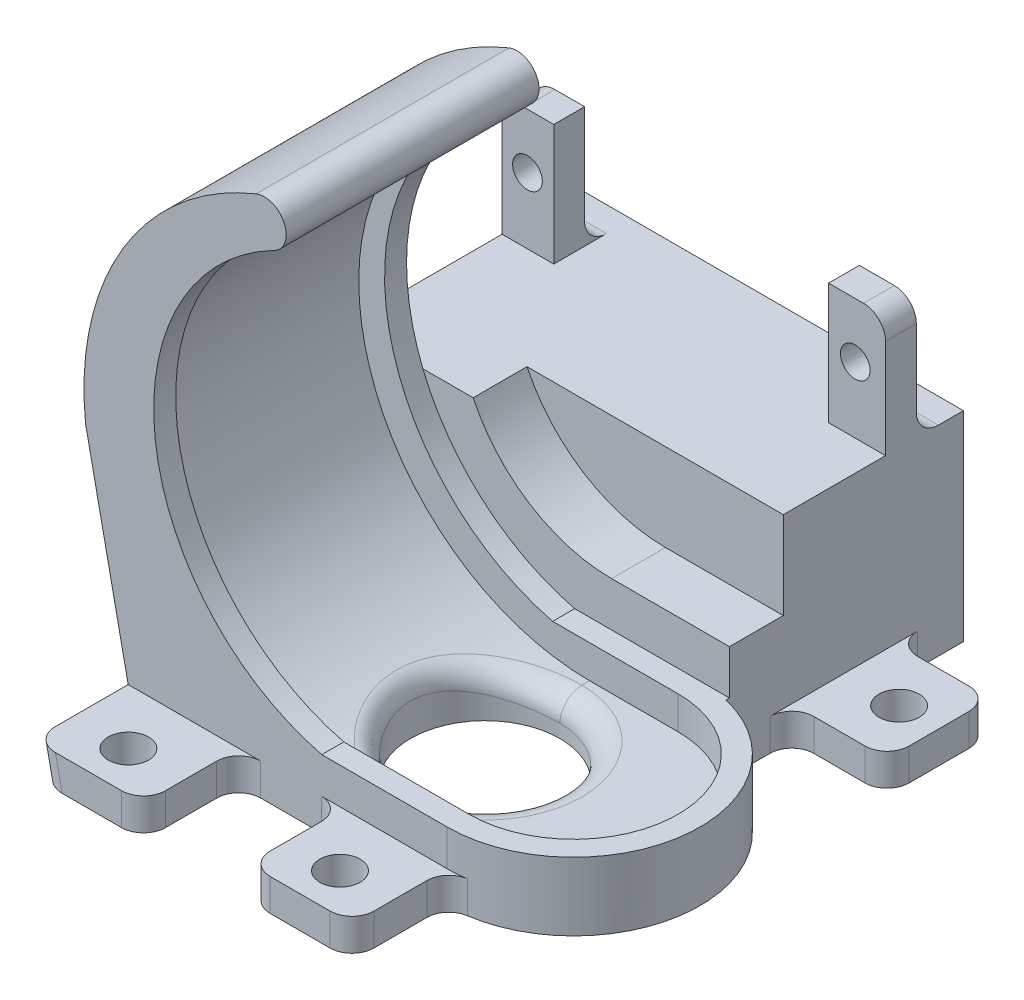
SolidWorks part; units mm, degrees
material "ABS"
ref_plane "Front Plane" through (0, 0, 0) normal (0, 0, 1) x (1, 0, 0)
ref_plane "Top Plane" through (0, 0, 0) normal (0, 1, 0) x (1, 0, 0)
ref_plane "Right Plane" through (0, 0, 0) normal (1, 0, 0) x (0, 0, -1)
sketch "Sketch1" plane through (0, 0, 0) normal (0, 1, 0) x (1, 0, 0)
  line L1 (-31.75, -12.065) -> (31.75, -12.065)
  line L2 (-31.75, -12.065) -> (-31.75, 12.065)
  line L3 (-31.75, 12.065) -> (31.75, 12.065)
  line L4 (31.75, -12.065) -> (31.75, 12.065)
  line L5 (-31.75, -12.065) -> (31.75, 12.065) construction
  line L6 (-31.75, 12.065) -> (31.75, -12.065) construction
  point P0 (0, 0)
  dimension "D1" = 24.13
  dimension "D2" = 63.5
extrude "Boss-Extrude1" add sketch "Sketch1" along normal blind 4.064
sketch "Sketch2" plane through (0, 0, 0) normal (0, 0, 1) x (1, 0, 0)
  line L0 (0, -2.2352) -> (0, 2.2352) construction
  line L1 (-31.75, 4.064) -> (31.75, 4.064) construction
  line L3 (-31.75, 4.064) -> (31.75, 4.064) construction
  line L4 (0, 4.064) -> (-26.7168, 4.064)
  line L5 (-31.571, 27.3677) -> (-26.7168, 4.064)
  arc A0 (-9.9723, 55.4695) -> (0, 4.064) centre (0, 30.734) ccw
  arc A1 (-11.8717, 60.181) -> (-31.571, 27.3677) centre (0, 30.734) ccw
  arc A2 (-9.9723, 55.4695) -> (-11.8717, 60.181) centre (-10.922, 57.8252) ccw
  dimension "D1" = 53.34
  dimension "D2" = 63.5
  dimension "D3" = 10.922
  dimension "D4" = 23.3037
  dimension "D5" = 23.8039
extrude "Boss-Extrude2" add sketch "Sketch2" along normal up to surface and the other way up to surface up to face at (0, 2.032, 12.065) other way up to face at (0, 2.032, -12.065)
sketch "Sketch4" plane through (0, 4.064, 0) normal (0, 1, 0) x (1, 0, 0)
  circle A0 centre (0, 0) radius 8.636
  dimension "D1" = 17.272
extrude "Cut-Extrude1" cut sketch "Sketch4" against normal through all and the other way blind 4.064
fillet "Fillet1" radius 2.54 2 edges at (8.636, 4.064, 0) (-8.5992, 5.4884, 0.7963)
sketch "Sketch6" plane through (0, 0, 12.065) normal (0, 0, 1) x (1, 0, 0)
  line L0 (-31.75, 4.064) -> (-26.7168, 4.064)
  line L1 (-26.7168, 4.064) -> (-25.8702, 0)
  line L2 (-25.8702, 0) -> (-31.75, 0)
  line L3 (-31.75, 4.064) -> (-31.75, 0) construction
  line L4 (-31.75, 0) -> (-31.75, 4.064)
  dimension "D1" = 4.1512
extrude "Cut-Extrude2" cut sketch "Sketch6" against normal through all
sketch "Sketch8" plane through (0, 0, 12.065) normal (0, 0, 1) x (1, 0, 0)
  line L0 (31.75, 0) -> (31.75, 7.874)
  line L1 (0, 4.064) -> (31.75, 4.064) construction
  line L2 (31.75, 0) -> (-25.8702, 0)
  line L3 (-25.8702, 0) -> (-31.571, 27.3677)
  line L4 (31.75, 7.874) -> (-23.9497, 7.874) construction
  line L5 (-4.2746, 7.874) -> (31.75, 7.874)
  arc A0 (-31.571, 27.3677) -> (-11.8717, 60.181) centre (0, 30.734) cw
  arc A1 (-11.8717, 60.181) -> (-9.9723, 55.4695) centre (-10.922, 57.8252) cw
  arc A2 (-9.9723, 55.4695) -> (-4.2746, 7.874) centre (1.9655, 32.7598) ccw
  dimension "D1" = 3.81
extrude "Boss-Extrude3" add sketch "Sketch8" along normal blind 2.54
sketch "Sketch9" plane through (0, 0, -12.065) normal (0, 0, -1) x (-1, 0, 0)
  line L0 (-31.75, 0) -> (-31.75, 7.874)
  line L1 (-31.75, 7.874) -> (4.2746, 7.874)
  line L2 (-31.75, 0) -> (25.8702, 0)
  line L3 (25.8702, 0) -> (31.571, 27.3677)
  arc A0 (31.571, 27.3677) -> (11.8717, 60.181) centre (0, 30.734) ccw
  arc A2 (9.9723, 55.4695) -> (4.2746, 7.874) centre (-1.9655, 32.7598) cw
  arc A3 (11.8717, 60.181) -> (9.9723, 55.4695) centre (10.922, 57.8252) ccw
extrude "Boss-Extrude4" add sketch "Sketch9" along normal blind 2.54
sketch "Sketch10" plane through (0, 4.064, 0) normal (0, 1, 0) x (1, 0, 0)
  line L0 (10.2183, 14.605) -> (10.2183, -14.605) construction
  line L3 (-4.2746, 14.605) -> (31.75, 14.605) construction
  line L4 (31.75, -14.605) -> (-4.2746, -14.605) construction
  line L5 (10.2183, 14.605) -> (10.2183, 12.065)
  line L6 (10.2183, -12.065) -> (10.2183, -14.605)
  arc A2 (10.2183, 14.605) -> (10.2183, -14.605) centre (10.2183, 0) cw
  arc A3 (10.2183, -12.065) -> (10.2183, 12.065) centre (10.2183, 0) ccw
extrude "Boss-Extrude5" add sketch "Sketch10" along normal blind 3.81
sketch "Sketch11" plane through (0, 7.874, 0) normal (0, 1, 0) x (1, 0, 0)
  line L0 (10.2183, 12.065) -> (10.2183, -12.065) construction
  line L1 (10.2183, 14.605) -> (10.2183, -14.605) construction
  line L2 (-4.2746, 14.605) -> (31.75, 14.605) construction
  line L3 (31.75, -14.605) -> (-4.2746, -14.605) construction
  line L4 (10.2183, 14.605) -> (31.75, 14.605)
  line L5 (31.75, 14.605) -> (31.75, -14.605)
  line L6 (31.75, -14.605) -> (10.2183, -14.605)
  arc A0 (10.2183, -14.605) -> (10.2183, 14.605) centre (10.2183, 0) ccw
extrude "Cut-Extrude3" cut sketch "Sketch11" against normal through all
sketch "Sketch12" plane through (0, 0, 0) normal (0, -1, 0) x (1, 0, 0)
  line L0 (-25.8702, -14.605) -> (-31.571, -14.605) construction
  line L1 (-31.2166, -14.605) -> (13.6144, -14.605)
  line L2 (-31.2166, -14.605) -> (-31.2166, -41.632)
  line L3 (-31.2166, -41.632) -> (13.6144, -41.632)
  line L4 (13.6144, -14.605) -> (13.6144, -41.632)
extrude "Boss-Extrude6" add sketch "Sketch12" against normal up to surface (23.114 mm away) up to face at (-6.2783, 14.6544, 12.065)
sketch "Sketch13" plane through (0, 0, 0) normal (0, -1, 0) x (1, 0, 0)
  line L0 (10.2183, -14.605) -> (13.6144, -14.605)
  line L1 (13.6144, -14.605) -> (13.6144, -13.3355)
  line L2 (13.6144, -13.3355) -> (10.2183, -14.605)
extrude "Boss-Extrude7" add sketch "Sketch13" against normal up to surface (7.874 mm away) up to face at (6.3056, 7.874, 0)
sketch "Sketch14" plane through (0, 0, -14.605) normal (0, 0, 1) x (1, 0, 0)
  line L0 (0, 13.0173) -> (18.6203, 13.0173)
  line L1 (18.6203, 13.0173) -> (17.7167, 30.734)
  arc A0 (17.7167, 30.734) -> (0, 13.0173) centre (0, 30.734) ccw
extrude "Cut-Extrude4" cut sketch "Sketch14" against normal up to surface (6.2198 mm away) up to face at (7.2796, 4.064, 0)
sketch "Sketch16" plane through (0, 0, -14.605) normal (0, 0, 1) x (1, 0, 0)
  line L0 (-31.2166, 23.114) -> (-30.685, 23.114)
  line L1 (-30.685, 23.114) -> (-25.8702, 0)
  line L2 (-25.8702, 0) -> (-31.2166, 0)
  line L3 (-31.2166, 0) -> (-31.2166, 23.114)
extrude "Cut-Extrude5" cut sketch "Sketch16" against normal up to surface (27.027 mm away) up to face at (-8.8011, 11.557, -41.632)
sketch "Sketch17" plane through (0, 23.114, 0) normal (0, 1, 0) x (1, 0, 0)
  line L0 (13.6144, 41.632) -> (13.6144, 20.8248) construction
  line L1 (6.6167, 32.6358) -> (13.6144, 32.6358)
  line L2 (6.6167, 32.6358) -> (6.6167, 36.1918)
  line L3 (6.6167, 36.1918) -> (13.6144, 36.1918)
  line L4 (13.6144, 32.6358) -> (13.6144, 36.1918)
  dimension "D1" = 3.556
extrude "Boss-Extrude8" add sketch "Sketch17" along normal blind 13.97
sketch "Sketch18" plane through (0, 23.114, 0) normal (0, 1, 0) x (1, 0, 0)
  line L0 (-30.685, 41.632) -> (-30.685, 14.605) construction
  line L1 (-24.2951, 32.6358) -> (-30.685, 32.6358)
  line L2 (-24.2951, 32.6358) -> (-24.2951, 36.1918)
  line L3 (-24.2951, 36.1918) -> (-30.685, 36.1918)
  line L4 (-30.685, 32.6358) -> (-30.685, 36.1918)
  dimension "D1" = 3.556
extrude "Boss-Extrude9" add sketch "Sketch18" along normal blind 13.97
sketch "Sketch19" plane through (0, 37.084, 0) normal (0, 1, 0) x (1, 0, 0)
  line L0 (-24.2951, 36.1918) -> (6.6167, 36.1918) construction
  line L1 (6.6167, 32.6358) -> (13.6144, 32.6358) construction
  line L2 (-24.7142, 39.7478) -> (7.0358, 39.7478)
  line L3 (-24.7142, 39.7478) -> (-24.7142, 32.6358)
  line L4 (-24.7142, 32.6358) -> (7.0358, 32.6358)
  line L5 (7.0358, 39.7478) -> (7.0358, 32.6358)
  line L6 (-24.7142, 39.7478) -> (7.0358, 32.6358) construction
  line L7 (-24.7142, 32.6358) -> (7.0358, 39.7478) construction
  point P4 (-8.8392, 36.1918)
  dimension "D1" = 31.75
extrude "Cut-Extrude6" cut sketch "Sketch19" against normal up to surface (13.97 mm away) up to face at (-10.4957, 23.114, -29.6026)
sketch "Sketch20" plane through (0, 0, -36.1918) normal (0, 0, -1) x (-1, 0, 0)
  circle A0 centre (27.7559, 30.734) radius 1.7145
  circle A1 centre (-10.1155, 30.734) radius 1.7145
  dimension "D1" = 3.429
  dimension "D2" = 3.429
extrude "Cut-Extrude7" cut sketch "Sketch20" against normal up to surface (3.556 mm away)
fillet "Fillet2" radius 2.54 1 edges at (10.3251, 23.114, -36.1918)
fillet "Fillet3" radius 2.54 1 edges at (-27.6996, 23.114, -36.1918)
fillet "Fillet4" radius 2.54 2 edges at (13.6144, 37.084, -34.4138) (-30.685, 37.084, -34.4138)
sketch "Sketch21" plane through (0, 0, 0) normal (0, -1, 0) x (1, 0, 0)
  line L0 (13.6144, -41.632) -> (13.6144, -14.2047) construction
  line L1 (-25.8702, 14.605) -> (-13.8702, 14.605)
  line L2 (-25.8702, 14.605) -> (-25.8702, 25.605)
  line L3 (-25.8702, 25.605) -> (-13.8702, 25.605)
  line L4 (-13.8702, 14.605) -> (-13.8702, 25.605)
  line L5 (10.2183, 14.605) -> (-1.7817, 14.605)
  line L6 (10.2183, 14.605) -> (10.2183, 25.605)
  line L7 (10.2183, 25.605) -> (-1.7817, 25.605)
  line L8 (-1.7817, 14.605) -> (-1.7817, 25.605)
  line L9 (13.6144, -21.8123) -> (24.6144, -21.8123)
  line L10 (13.6144, -21.8123) -> (13.6144, -33.8123)
  line L11 (13.6144, -33.8123) -> (24.6144, -33.8123)
  line L12 (24.6144, -21.8123) -> (24.6144, -33.8123)
  dimension "D1" = 11
  dimension "D2" = 11
  dimension "D3" = 12
  dimension "D4" = 12
  dimension "D5" = 12
  dimension "D6" = 11
extrude "Boss-Extrude10" add sketch "Sketch21" against normal blind 3.7
sketch "Sketch22" plane through (0, 0, 14.605) normal (0, 0, 1) x (1, 0, 0)
  line L0 (-25.8702, 3.7) -> (-26.6409, 3.7)
  line L1 (-31.571, 27.3677) -> (-25.8702, 0) construction
  line L2 (-26.6409, 3.7) -> (-25.8702, 0)
  line L3 (-25.8702, 0) -> (-25.8702, 3.7)
extrude "Boss-Extrude11" add sketch "Sketch22" along normal up to surface (11 mm away) up to face at (-19.8702, 1.85, 25.605)
fillet "Fillet5" radius 2.54 11 edges at (13.6144, 1.85, -33.8123) (24.6144, 1.85, -33.8123) (24.6144, 1.85, -21.8123) (13.6144, 1.85, -21.8123) (10.2183, 1.85, 14.605) (10.2183, 1.85, 25.605) (-1.7817, 1.85, 25.605) (-1.7817, 1.85, 14.605) (-13.8702, 1.85, 14.605) (-13.8702, 1.85, 25.605) (-26.2556, 1.85, 25.605)
sketch "Sketch23" plane through (0, 3.7, 0) normal (0, 1, 0) x (1, 0, 0)
  line L0 (-20.2283, -25.605) -> (-20.2283, -14.605) construction
  line L1 (-16.4102, -25.605) -> (-24.0464, -25.605) construction
  line L2 (-31.75, -14.605) -> (-11.8717, -14.605) construction
  line L3 (4.2183, -25.605) -> (4.2183, -14.605) construction
  line L4 (7.6783, -25.605) -> (0.7583, -25.605) construction
  line L5 (10.2183, -14.605) -> (-4.2746, -14.605) construction
  line L6 (24.6144, 27.8123) -> (13.6144, 27.8123) construction
  line L7 (24.6144, 31.2723) -> (24.6144, 24.3523) construction
  line L8 (13.6144, 32.6358) -> (13.6144, 20.8248) construction
  line L9 (-20.2283, -20.994) -> (-20.2283, -18.669) construction
  line L10 (4.2183, -20.994) -> (4.2183, -18.669) construction
  line L11 (20.0034, 27.8123) -> (17.6784, 27.8123) construction
  circle A0 centre (20.0034, 27.8123) radius 2.325
  circle A1 centre (-20.2283, -20.994) radius 2.325
  circle A2 centre (4.2183, -20.994) radius 2.325
  dimension "D1" = 4.65
  dimension "D2" = 4.064
  dimension "D3" = 4.064
  dimension "D4" = 4.064
extrude "Cut-Extrude8" cut sketch "Sketch23" against normal through all
